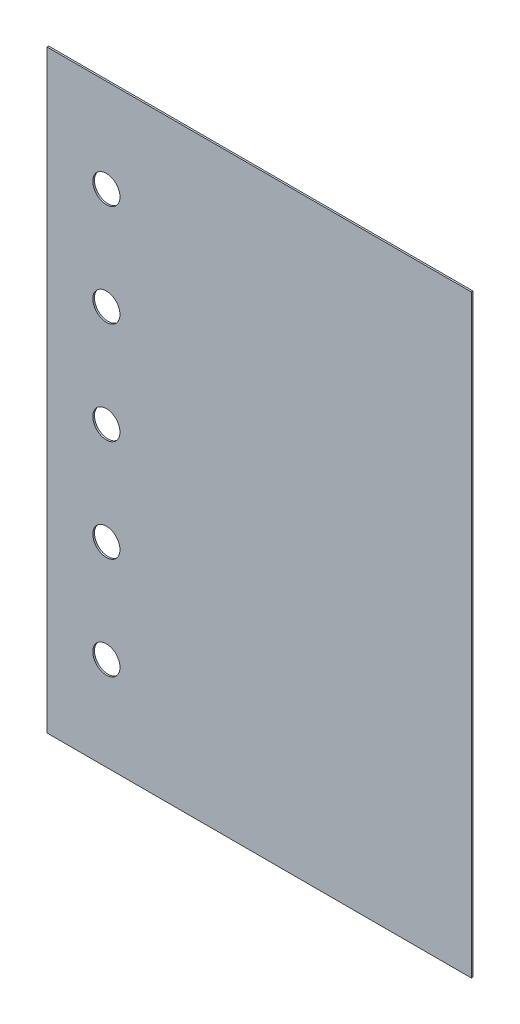
SolidWorks part; units mm, degrees
ref_plane "Front Plane" through (0, 0, 0) normal (1, 0, 0) x (0, 1, 0)
ref_plane "Top Plane" through (0, 0, 0) normal (0, 0, 1) x (0, 1, 0)
ref_plane "Right Plane" through (0, 0, 0) normal (0, 1, 0) x (-1, 0, 0)
sketch "Sketch1" plane through (0, 0, 0) normal (0, 0, 1) x (0, 1, 0)
  line L1 (-175, -125) -> (175, -125)
  line L2 (-175, -125) -> (-175, 125)
  line L3 (-175, 125) -> (175, 125)
  line L4 (175, -125) -> (175, 125)
  line L5 (-175, -125) -> (175, 125) construction
  line L6 (-175, 125) -> (175, -125) construction
  point P0 (0, 0)
  dimension "D1" = 350
  dimension "D2" = 250
extrude "Boss-Extrude1" add sketch "Sketch1" along normal blind 1
sketch "Sketch2" plane through (0, 0, 1) normal (0, 0, 1) x (0, -1, 0)
  line L0 (-160, -125) -> (-160, 125) construction
  line L1 (-175, -125) -> (175, -125) construction
  line L2 (175, 125) -> (-175, 125) construction
  line L3 (-175, 125) -> (-175, -125) construction
  circle A0 centre (-160, -60) radius 8
  circle A1 centre (-160, -30) radius 8
  circle A2 centre (-160, 0) radius 8
  circle A3 centre (-160, 30) radius 8
  circle A4 centre (-160, 60) radius 8
  dimension "D1" = 16
  dimension "D2" = 30
  dimension "D3" = 30
  dimension "D4" = 30
  dimension "D5" = 30
  dimension "D6" = 15
extrude "Cut-Extrude1" [suppressed] cut sketch "Sketch2" against normal through all
sketch "Sketch3" plane through (0, 0, 1) normal (0, 0, 1) x (0, -1, 0)
  line L0 (-175, -125) -> (175, -125) construction
  circle A0 centre (120, -90) radius 8
  circle A1 centre (60, -90) radius 8
  circle A2 centre (0, -90) radius 8
  circle A3 centre (-60, -90) radius 8
  circle A4 centre (-120, -90) radius 8
  point P7 (0, -125)
  dimension "D1" = 16
  dimension "D4" = 5
  dimension "D2" = 35
extrude "Cut-Extrude2" cut sketch "Sketch3" against normal through all
